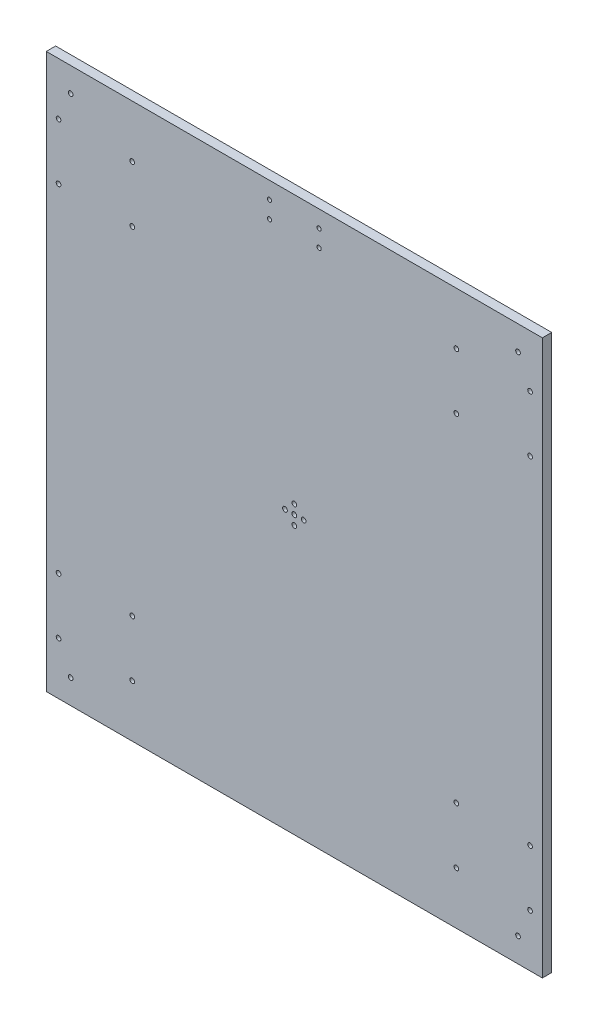
SolidWorks part; units mm, degrees
ref_plane "Спереди" through (0, 0, 0) normal (0, 0, 1) x (1, 0, 0)
ref_plane "Сверху" through (0, 0, 0) normal (0, 1, 0) x (1, 0, 0)
ref_plane "Справа" through (0, 0, 0) normal (1, 0, 0) x (0, 0, -1)
sketch "Эскиз3" plane through (0, 0, 0) normal (0, 0, 1) x (1, 0, 0)
  line L0 (0, 0) -> (0, 10) construction
  line L5 (265, -296.15) -> (-265, -296.15)
  line L6 (265, -296.15) -> (265, 296.15)
  line L7 (265, 296.15) -> (-265, 296.15)
  line L8 (-265, -296.15) -> (-265, 296.15)
  line L9 (0, 0) -> (10, 0) construction
  line L10 (0, 0) -> (0, -10) construction
  line L11 (0, 0) -> (-10, 0) construction
  circle A0 centre (0, 0) radius 2.55
  circle A1 centre (0, 10) radius 2.55
  circle A2 centre (10, 0) radius 2.55
  circle A3 centre (0, -10) radius 2.55
  circle A4 centre (-10, 0) radius 2.55
  point P0 (0, 0)
  point P5 (-265, 0)
  point P6 (0, 296.15)
  point P21 (0, 0)
  dimension "D3" = 5.1
  dimension "D4" = 5.1
  dimension "D1" = 592.3
  dimension "D2" = 530
  dimension "D5" = 10
  dimension "D6" = 4
extrude "Бобышка-Вытянуть1" add sketch "Эскиз3" along normal blind 10
sketch "Эскиз4" plane through (0, 0, 10) normal (0, 0, 1) x (1, 0, 0)
  line L0 (265, 296.15) -> (-265, 296.15) construction
  line L1 (-265, 296.15) -> (-265, -296.15) construction
  circle A0 centre (-239, 270.15) radius 2.5
  dimension "D1" = 5
  dimension "D2" = 26
  dimension "D3" = 26
extrude "Вырез-Вытянуть1" cut sketch "Эскиз4" against normal through all contours A0
pattern_linear "Линейный массив1" count 2 spacing 478 along (1, 0, 0) count 2 spacing 540.3 along (0, -1, 0) of "Вырез-Вытянуть1"
sketch "Эскиз7" plane through (0, 0, 0) normal (0, 0, -1) x (-1, 0, 0)
  line L9 (-26.5, 278.15) -> (26.5, 278.15) construction
  line L10 (-26.5, 278.15) -> (-26.5, 260.15) construction
  line L11 (-26.5, 260.15) -> (26.5, 260.15) construction
  line L16 (26.5, 278.15) -> (26.5, 260.15) construction
  line L17 (-265, 296.15) -> (265, 296.15) construction
  circle A0 centre (-26.5, 278.15) radius 2.25
  circle A1 centre (26.5, 278.15) radius 2.25
  circle A2 centre (-26.5, 260.15) radius 2.25
  circle A3 centre (26.5, 260.15) radius 2.25
  point P4 (0, 260.15)
  dimension "D4" = 4.5
  dimension "D5" = 4.5
  dimension "D6" = 4.5
  dimension "D7" = 4.5
  dimension "D1" = 53
  dimension "D2" = 18
  dimension "D3" = 18
extrude "Вырез-Вытянуть2" cut sketch "Эскиз7" against normal through all
sketch "Эскиз8" plane through (0, 0, 0) normal (0, 0, -1) x (-1, 0, 0)
  line L0 (160, 170.15) -> (265, 250.15) construction
  line L1 (265, 250.15) -> (160, 250.15) construction
  line L2 (265, 250.15) -> (265, 170.15) construction
  line L3 (265, 170.15) -> (160, 170.15) construction
  line L4 (160, 250.15) -> (160, 170.15) construction
  line L5 (160, 250.15) -> (265, 170.15) construction
  line L6 (265, 296.15) -> (265, -296.15) construction
  line L7 (-265, 296.15) -> (265, 296.15) construction
  circle A0 centre (173.125, 180.15) radius 2.5
  circle A1 centre (173.125, 240.15) radius 2.5
  circle A2 centre (251.875, 240.15) radius 2.5
  circle A3 centre (251.875, 180.15) radius 2.5
  dimension "D3" = 5
  dimension "D4" = 5
  dimension "D5" = 5
  dimension "D6" = 5
  dimension "D1" = 105
  dimension "D2" = 80
  dimension "D7" = 60
  dimension "D8" = 46
extrude "Вырез-Вытянуть3" cut sketch "Эскиз8" against normal through all
pattern_linear "Линейный массив2" count 2 spacing 420.3 along (0, -1, 0) count 2 spacing 424.995 along (1, 0, 0) of "Вырез-Вытянуть3"
equation "\"Ширина груза\"= 420"
equation "\"Глубина груза\"= 490"
equation "\"Высота груза\"= 297"
equation "\"Ширина ячейки\"= \"Ширина груза\" + 10"
equation "\"Глубина ячейки\"= \"Глубина груза\" + 10"
equation "\"Высота ячейки\"= \"Высота груза\" + 10 + 13"
equation "\"Колво ячеек ширина\"= 2"
equation "\"Колво ячеек высота\"= 2"
equation "\"Толщина стенки\"= 10"
equation "\"Крепление дверцы\"= 5"
equation "\"Ширина рейки\"= \"Толщина шестерни\""
equation "\"Высота рейки\"= 20"
equation "\"Высота пола\"= 20"
equation "\"Колво полозьев\"= 5"
equation "\"Отступ рейки\"= 20"
equation "\"Глубина каретки\"= \"Глубина ячейки\" + 30 + \"Мотор Y высота корпуса\" + 20"
equation "\"Длинна рейки\"= ( \"Ширина ячейки\" + \"Толщина стенки\" + \"Крепление дверцы\" ) * \"Колво ячеек ширина\" + \"Ширина ячейки выгрузки\" * \"Колво выгрузки\" + \"Толщина стенки\""
equation "\"Отступ шпильки\"= 26"
equation "\"Диаметр шпильки\"= 5"
equation "\"D1@Бобышка-Вытянуть1\" = \"Толщина стенки\""
equation "\"D1@Эскиз4\"= \"Диаметр шпильки\""
equation "\"D2@Эскиз4\"=\"Отступ шпильки\""
equation "\"D3@Эскиз4\"= \"Отступ шпильки\""
equation "\"D2@Эскиз3\"=\"Ширина ячейки\" + \"Ширина пластины\" * 2"
equation "\"D1@Эскиз3\"=\"Глубина каретки\" "
equation "\"D3@Линейный массив1\"=\"Ширина ячейки\"  +\"Ширина пластины\" *2 - \"Отступ шпильки\" * 2"
equation "\"D4@Линейный массив1\"=\"Глубина каретки\" + \"Ширина рейки\" * 2 - \"Отступ шпильки\" * 2 - \"Ширина рейки\" * 2"
equation "\"Длинна шпильки\"= ( \"Высота ячейки\" + \"Толщина стенки\" + \"Высота пола\" ) * \"Колво ячеек высота\" + ( \"Толщина стенки\" + \"Отступ рейки\" ) * 2 "
equation "\"Ширина пластины\"= 50  "
equation "\"Высота зона выгрузки\"= \"Высота ячейки\" * 2 + \"Толщина стенки\" * 2"
equation "\"Колво выгрузки\"= 1"
equation "\"Отступ крепления мотора фиксации\" = 30"
equation "\"Мотор X ширина корпуса\"= 42.3"
equation "\"Мотор X высота корпуса\"= 42.3"
equation "\"Мотор X длина корпуса\"= 40"
equation "\"Мотор X вылет вала\"= 19.8"
equation "\"Мотор Y ширина корпуса\"= 42.3"
equation "\"Мотор Y высота корпуса\"= 42.3"
equation "\"Мотор Y длина корпуса\"= 48"
equation "\"Мотор Y вылет вала\"= 30"
equation "\"Мотор Z ширина корпуса\"= 42"
equation "\"Мотор Z высота корпуса\"= 42"
equation "\"Мотор Z длина корпуса\"= 40"
equation "\"Мотор Z вылет вала\"= 23"
equation "\"Мотор диаметр вала ПРЕДВ\"= 5"
equation "\"Мотор шаг крепления ПРЕДВ\"= 31"
equation "\"Мотор диаметр отверстий ПРЕДВ\"= 3"
equation "\"Мотор глубина отверстий ПРЕДВ\"= 4.5"
equation "\"Мотор диаметр буртика ПРЕДВ\"= 22"
equation "\"Мотор высота буртика ПРЕДВ\"= 2"
equation "\"Мотор диаметр шкива ПРЕДВ\"= 16"
equation "\"Мотор длина шкива ПРЕДВ\"= 12"
equation "\"Мотор отступ шкива ПРЕДВ\"= 5"
equation "\"Мотор X шаг градусов\"= 1.8"
equation "\"Мотор Y шаг градусов\"= 1.8"
equation "\"Мотор Z шаг градусов\"= 1.8"
equation "\"Мотор Y диаметр ротора\"= 25.78"
equation "\"Толщина шестерни\"= 10"
equation "\"Ширина ячейки выгрузки\"= \"Ширина ячейки\" + \"Толщина стенки\" + \"Отступ крепления мотора фиксации\"*2"
